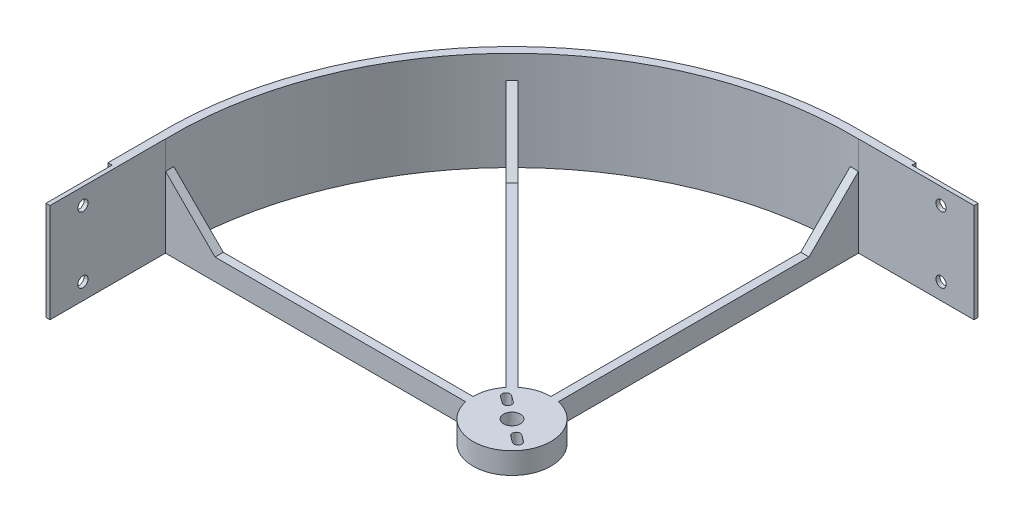
SolidWorks part; units mm, degrees
material "ABS"
ref_plane "Front Plane" through (0, 0, 0) normal (0, 0, 1) x (1, 0, 0)
ref_plane "Top Plane" through (0, 0, 0) normal (0, 1, 0) x (1, 0, 0)
ref_plane "Right Plane" through (0, 0, 0) normal (1, 0, 0) x (0, 0, -1)
sketch "Sketch1" plane through (0, 0, 0) normal (0, 1, 0) x (1, 0, 0)
  line L0 (0, 130.175) -> (0, 9.3426)
  line L1 (3.175, 9.3426) -> (3.175, 130.1363)
  line L2 (-92.0476, 92.0476) -> (0, 0) construction
  line L3 (-90.9182, 93.1633) -> (-5.7657, 8.0107)
  line L4 (-9.7388, -3.175) -> (-130.1363, -3.175)
  line L5 (-130.175, 0) -> (-9.3426, 0)
  line L6 (3.175, 9.3426) -> (3.175, 130.1363)
  line L7 (3.175, 130.1363) -> (3.175, 133.3122)
  line L8 (-130.1363, -3.175) -> (-133.3122, -3.175)
  line L9 (0, 0) -> (-130.175, 0) construction
  line L10 (-8.0089, 5.7638) -> (-93.1633, 90.9182)
  line L11 (0, 0) -> (0, 146.05) construction
  circle A0 centre (0, 0) radius 15
  arc A1 (3.175, 130.1363) -> (-130.1363, -3.175) centre (0, 0) ccw
  arc A2 (3.175, 133.3122) -> (-133.3122, -3.175) centre (0, 0) ccw
  point P21 (0, 0)
  dimension "D1" = 30
  dimension "D2" = 133.35
  dimension "D4" = 3.175
  dimension "D6" = 1.5875
  dimension "D3" = 3.175
  dimension "D7" = 1.5875
  dimension "D5" = 3.175
extrude "Boss-Extrude2" add sketch "Sketch1" along normal blind 8.255 contours A0
extrude "Boss-Extrude3" add sketch "Sketch1<6>" along normal blind 8.255 contours L5 A1 L4 A0 | L6 A1 L0 A0 | A1 L10 A0 region at (1.5882, 0, -72.5246) region at (-51.3161, 0, -51.3161) region at (-72.5246, 0, 1.5882)
sketch "Sketch1<6>" plane through (0, 0, 0) normal (0, 1, 0) x (1, 0, 0) same geometry as "Sketch1"
extrude "Boss-Extrude4" add sketch "Sketch1<7>" along normal blind 38.1 contours L7 A2 L8 A1 region at (-49.8095, 0, -122.3558)
sketch "Sketch1<7>" plane through (0, 0, 0) normal (0, 1, 0) x (1, 0, 0) same geometry as "Sketch1"
ref_plane "Plane1" through (-63.4806, 0, -63.4806) normal (0.7071, 0, 0.7071) x (0.7071, 0, -0.7071)
sketch "Sketch5" plane through (0, 8.255, 0) normal (0, 1, 0) x (1, 0, 0)
  line L0 (0, 0) -> (-92.0476, 92.0476) construction
  line L1 (0, 0) -> (15.8128, 15.8128) construction
  line L2 (-8.7797, 6.4967) -> (0, 0) construction
  line L3 (-6.3296, 4.6836) -> (-8.7797, 6.4967) construction
  line L4 (-7.2361, 3.4586) -> (-9.6862, 5.2716)
  line L5 (-5.4231, 5.9087) -> (-7.8732, 7.7217)
  line L6 (0, 0) -> (3.6216, 4.8943) construction
  line L7 (6.3296, -4.6836) -> (8.7797, -6.4967) construction
  line L8 (5.4231, -5.9087) -> (7.8732, -7.7217)
  line L9 (7.2361, -3.4586) -> (9.6862, -5.2716)
  line L10 (-90.9182, 93.1633) -> (-9.4245, 11.6696) construction
  arc A0 (5.4231, -5.9087) -> (7.2361, -3.4586) centre (6.3296, -4.6836) cw
  arc A1 (-7.2361, 3.4586) -> (-5.4231, 5.9087) centre (-6.3296, 4.6836) ccw
  arc A2 (-7.8732, 7.7217) -> (-9.6862, 5.2716) centre (-8.7797, 6.4967) ccw
  arc A3 (9.6862, -5.2716) -> (7.8732, -7.7217) centre (8.7797, -6.4967) cw
  circle A6 centre (0, 0) radius 3.25
  point P8 (-7.5546, 5.5901)
  point P17 (7.5546, -5.5901)
  point P18 (0, 0)
  dimension "D3" = 3.048
  dimension "D1" = 7.874
  dimension "D2" = 3.048
  dimension "D4" = 8.5
extrude "Cut-Extrude3" cut sketch "Sketch5" against normal blind 63.5
sketch "Sketch6" plane through (0, 0, 3.175) normal (0, 0, 1) x (1, 0, 0)
  line L0 (-14.6601, 0) -> (-133.3122, 0) construction
  line L1 (-130.1363, 38.1) -> (-131.7242, 38.1)
  line L2 (-130.1363, 38.1) -> (-130.1363, 0)
  line L3 (-130.1363, 0) -> (-131.7242, 0)
  line L4 (-131.7242, 38.1) -> (-131.7242, 0)
  line L5 (-130.1363, 38.1) -> (-133.3122, 38.1) construction
  point P7 (-131.7242, 38.1)
sketch "Sketch7" plane through (3.175, 0, 0) normal (1, 0, 0) x (0, 0, -1)
  line L0 (14.6601, 0) -> (133.3122, 0) construction
  line L1 (130.1363, 38.1) -> (131.7242, 38.1)
  line L2 (130.1363, 38.1) -> (130.1363, 0)
  line L3 (130.1363, 0) -> (131.7242, 0)
  line L4 (131.7242, 38.1) -> (131.7242, 0)
  line L5 (130.1363, 38.1) -> (133.3122, 38.1) construction
  line L6 (130.1363, 38.1) -> (130.1363, 8.255) construction
  point P7 (131.7242, 38.1)
ref_plane "Plane2" through (0, 0, 0) normal (0, 0, -1) x (-1, 0, 0)
sketch "Sketch10" plane through (0, 0, 0) normal (0, 0, -1) x (-1, 0, 0)
  line L0 (130.175, 27.305) -> (130.175, 8.255)
  line L4 (130.175, 8.255) -> (130.175, 38.1) construction
  line L5 (130.175, 8.255) -> (111.125, 8.255)
  line L6 (130.175, 8.255) -> (15, 8.255) construction
  line L7 (111.125, 8.255) -> (130.175, 27.305)
  dimension "D1" = 19.05
  dimension "D2" = 45
extrude "Boss-Extrude9" add sketch "Sketch10" against normal blind 3.175
ref_plane "Plane3" through (1.1225, 0, -1.1225) normal (0.7071, 0, -0.7071) x (-0.7071, 0, -0.7071)
ref_plane "Plane4" through (0, 0, 0) normal (-1, 0, 0) x (0, 0, 1)
sketch "Sketch13" plane through (0, 0, 0) normal (-1, 0, 0) x (0, 0, 1)
  line L0 (-130.175, 27.305) -> (-111.125, 8.255)
  line L1 (-130.175, 27.305) -> (-130.175, 8.255)
  line L2 (-130.175, 8.255) -> (-15, 8.255) construction
  line L3 (-130.175, 8.255) -> (-111.125, 8.255)
  line L4 (-130.175, 38.1) -> (-130.175, 8.255) construction
  dimension "D1" = 45
  dimension "D2" = 19.05
extrude "Boss-Extrude11" add sketch "Sketch13" against normal blind 3.175
sketch "Sketch14" plane through (1.1225, 0, -1.1225) normal (0.7071, 0, -0.7071) x (-0.7071, 0, -0.7071)
  line L0 (133.3403, 8.255) -> (111.1153, 8.255)
  line L1 (130.1653, 8.255) -> (14.9158, 8.255) construction
  line L2 (133.3403, 8.255) -> (133.3403, 32.3947)
  line L3 (133.3403, 32.3947) -> (111.1153, 8.255)
  dimension "D1" = 22.225
extrude "Boss-Extrude14" add sketch "Sketch14" against normal blind 3.175
ref_plane "Plane5" through (-131.7242, 0, 0) normal (-1, 0, 0) x (0, -1, 0)
sketch "Sketch15" plane through (-131.7242, 0, 0) normal (-1, 0, 0) x (0, -1, 0)
  line L1 (-38.1, 47.625) -> (0, 47.625)
  line L2 (-38.1, 47.625) -> (-38.1, 3.175)
  line L3 (-38.1, 3.175) -> (0, 3.175)
  line L4 (0, 47.625) -> (0, 3.175)
  dimension "D1" = 44.45
extrude "Boss-Extrude15" add sketch "Sketch15" against normal blind 1.524
ref_plane "Plane6" through (0, 0, -131.7242) normal (0, 0, -1) x (0, -1, 0)
sketch "Sketch16" plane through (0, 0, -131.7242) normal (0, 0, -1) x (0, -1, 0)
  line L1 (-38.1, -3.175) -> (0, -3.175)
  line L2 (-38.1, -3.175) -> (-38.1, -47.625)
  line L3 (-38.1, -47.625) -> (0, -47.625)
  line L4 (0, -3.175) -> (0, -47.625)
  dimension "D1" = 44.45
extrude "Boss-Extrude16" add sketch "Sketch16" against normal blind 1.524
sketch "Sketch17" plane through (0, 0, -131.7242) normal (0, 0, -1) x (-1, 0, 0)
  line L1 (-3.175, 38.1) -> (-47.625, 38.1) construction
  line L2 (19.05, 19.05) -> (-47.625, 19.05) construction
  line L3 (-47.625, 38.1) -> (-47.625, 0) construction
  circle A0 centre (-34.925, 31.75) radius 1.985
  circle A1 centre (-34.925, 6.35) radius 1.985
  dimension "D1" = 12.7
  dimension "D3" = 3.97
  dimension "D2" = 6.35
extrude "Cut-Extrude4" cut sketch "Sketch17" against normal blind 2.54
sketch "Sketch18" plane through (-131.7242, 0, 0) normal (-1, 0, 0) x (0, 0, 1)
  line L1 (25.4, 19.05) -> (47.625, 19.05) construction
  line L2 (47.625, 0) -> (47.625, 38.1) construction
  line L3 (47.625, 0) -> (47.625, 38.1) construction
  circle A0 centre (34.925, 31.75) radius 1.985
  circle A1 centre (34.925, 6.35) radius 1.985
  dimension "D1" = 3.97
  dimension "D2" = 12.7
  dimension "D3" = 12.7
extrude "Cut-Extrude5" cut sketch "Sketch18" against normal blind 2.54
sketch "Sketch19" plane through (-131.7242, 0, 0) normal (-1, 0, 0) x (0, 0, 1)
  line L0 (3.175, 0) -> (47.625, 0) construction
  line L1 (3.175, 38.1) -> (22.225, 38.1)
  line L2 (3.175, 38.1) -> (3.175, 0)
  line L3 (3.175, 0) -> (22.225, 0)
  line L4 (22.225, 38.1) -> (22.225, 0)
  dimension "D1" = 19.05
extrude "Boss-Extrude17" add sketch "Sketch19" along normal up to vertex (1.588 mm away) up to point (-133.3122, 0, 3.175)
sketch "Sketch20" plane through (0, 0, -131.7242) normal (0, 0, -1) x (-1, 0, 0)
  line L0 (-47.625, 0) -> (-3.175, 0) construction
  line L1 (-3.175, 38.1) -> (-22.225, 38.1)
  line L2 (-3.175, 38.1) -> (-3.175, 0)
  line L3 (-3.175, 0) -> (-22.225, 0)
  line L4 (-22.225, 38.1) -> (-22.225, 0)
  dimension "D1" = 19.05
extrude "Boss-Extrude18" add sketch "Sketch20" along normal up to vertex (1.588 mm away) up to point (3.175, 0, -133.3122)
